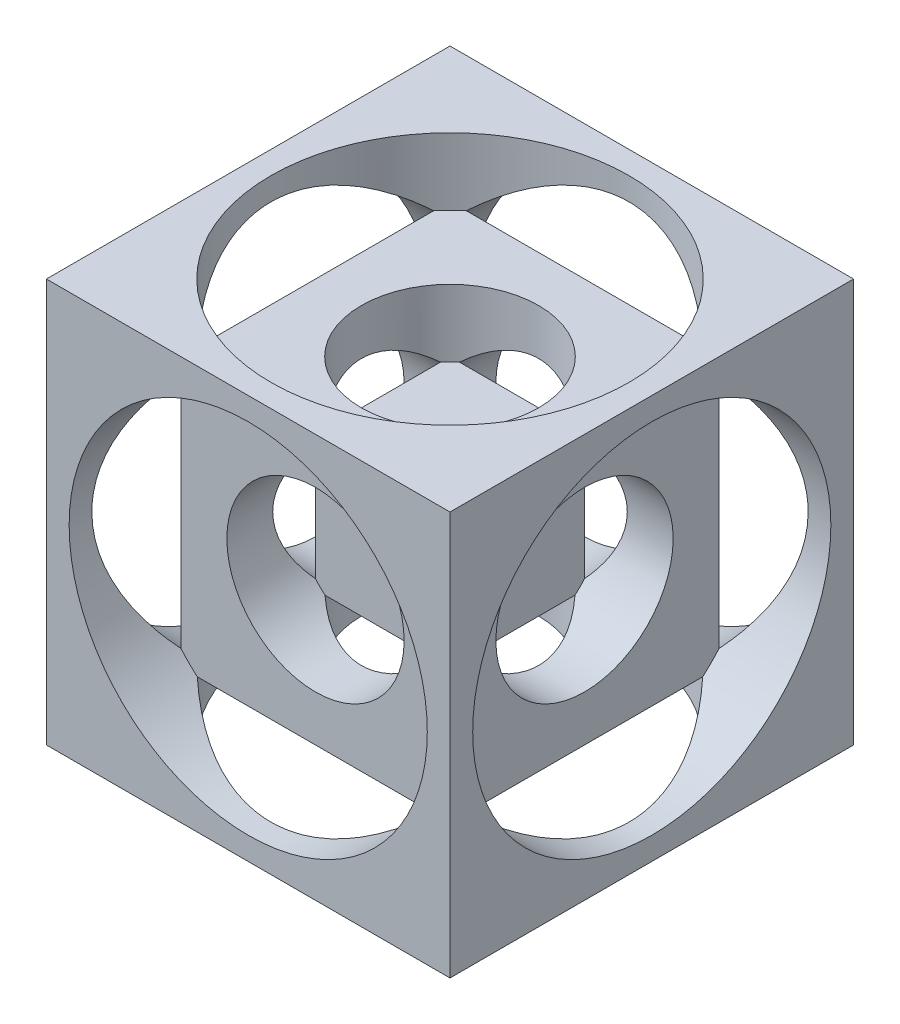
SolidWorks part; units mm, degrees
ref_plane "Front Plane" through (0, 0, 0) normal (0, 0, 1) x (1, 0, 0)
ref_plane "Top Plane" through (0, 0, 0) normal (0, 1, 0) x (1, 0, 0)
ref_plane "Right Plane" through (0, 0, 0) normal (1, 0, 0) x (0, 0, -1)
sketch "Sketch1" plane through (0, 0, 0) normal (0, 0, 1) x (1, 0, 0)
  line L1 (-22.86, -22.86) -> (22.86, -22.86)
  line L2 (-22.86, -22.86) -> (-22.86, 22.86)
  line L3 (-22.86, 22.86) -> (22.86, 22.86)
  line L4 (22.86, -22.86) -> (22.86, 22.86)
  line L5 (-22.86, -22.86) -> (22.86, 22.86) construction
  line L6 (-22.86, 22.86) -> (22.86, -22.86) construction
  point P0 (0, 0)
  dimension "D1" = 45.72
extrude "Boss-Extrude1" add sketch "Sketch1" against normal blind 22.86 and the other way blind 22.86
sketch "Sketch3" plane through (0, 0, 22.86) normal (0, 0, 1) x (1, 0, 0)
  line L0 (-15.24, -15.24) -> (-15.24, 15.24)
  line L1 (-7.62, -7.62) -> (7.62, -7.62)
  line L2 (-7.62, -7.62) -> (-7.62, 7.62)
  line L3 (-7.62, 7.62) -> (7.62, 7.62)
  line L4 (7.62, -7.62) -> (7.62, 7.62)
  line L5 (-7.62, -7.62) -> (7.62, 7.62) construction
  line L6 (-7.62, 7.62) -> (7.62, -7.62) construction
  line L7 (-15.24, 15.24) -> (15.24, 15.24)
  line L8 (15.24, -15.24) -> (15.24, 15.24)
  line L9 (-15.24, -15.24) -> (15.24, -15.24)
  point P0 (0, 0)
  dimension "D1" = 15.24
  dimension "D2" = 7.62
sketch "Sketch4" plane through (0, 0, 22.86) normal (0, 0, 1) x (1, 0, 0)
  circle A0 centre (0, 0) radius 20.2872
extrude "Cut-Extrude1" cut sketch "Sketch4" against normal blind 7.62
sketch "Sketch5" plane through (0, 0, 22.86) normal (0, 0, 1) x (1, 0, 0)
  circle A0 centre (0, 0) radius 10.0416
extrude "Cut-Extrude2" cut sketch "Sketch5" against normal blind 15.24
ref_axis "Axis1" through (-25.146, 0, 0) along (1, 0, 0)
ref_axis "Axis2" through (0, 25.146, 0) along (0, -1, 0)
pattern_circular "CirPattern1" count 4 every 90 about axis through (0, 25.146, 0) along (0, -1, 0) of "Cut-Extrude2", "Cut-Extrude1"
pattern_circular "CirPattern2" count 2 every 90 about axis through (-25.146, 0, 0) along (1, 0, 0) of "CirPattern1"
